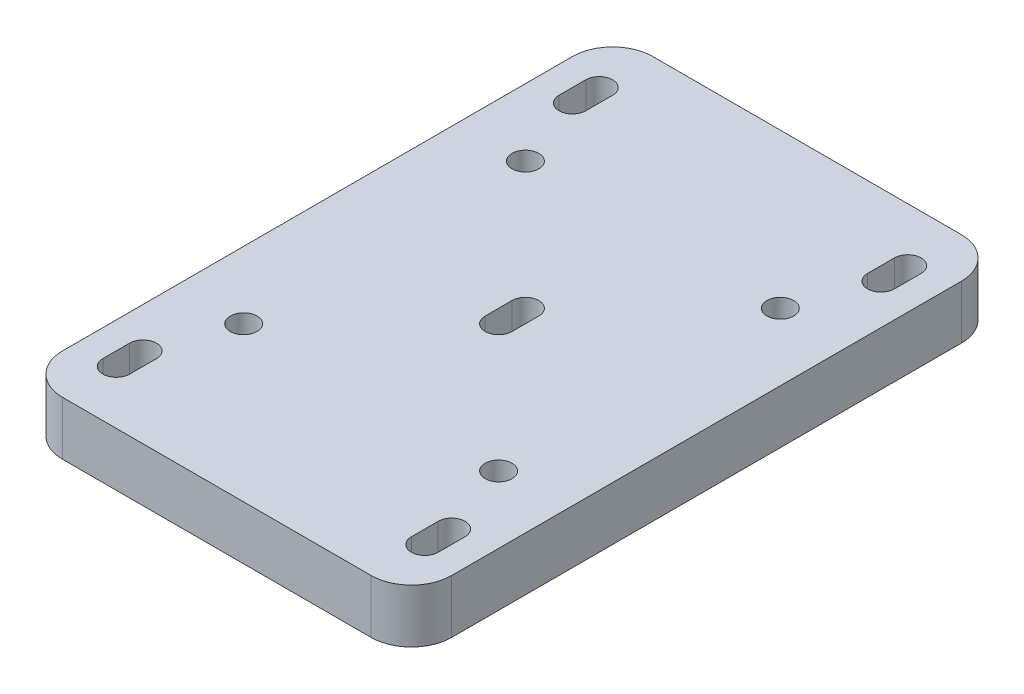
SolidWorks part; units mm, degrees
ref_plane "Front Plane" through (0, 0, 0) normal (0, 0, 1) x (1, 0, 0)
ref_plane "Top Plane" through (0, 0, 0) normal (0, 1, 0) x (1, 0, 0)
ref_plane "Right Plane" through (0, 0, 0) normal (1, 0, 0) x (0, 0, -1)
sketch "Sketch1" plane through (0, 0, 0) normal (0, 1, 0) x (1, 0, 0)
  line L1 (0, 0) -> (92.075, 0)
  line L2 (0, 0) -> (0, 139.7)
  line L3 (0, 139.7) -> (92.075, 139.7)
  line L4 (92.075, 0) -> (92.075, 139.7)
  dimension "D1" = 139.7
  dimension "D2" = 92.075
extrude "Boss-Extrude1" add sketch "Sketch1" along normal blind 12.7
hole_wizard "1/4 (0.25) Diameter Hole1" positions "Sketch5" profile "Sketch6" hole size "1/4" standard "ANSI Inch" end condition through all
sketch "Sketch5" plane through (0, 12.7, 0) normal (0, 1, 0) x (1, 0, 0)
  line L10 (0, 139.7) -> (92.075, 0) construction
  line L13 (15.875, 36.5125) -> (76.2, 36.5125) construction
  line L14 (15.875, 36.5125) -> (15.875, 103.1875) construction
  line L15 (15.875, 103.1875) -> (76.2, 103.1875) construction
  line L16 (76.2, 36.5125) -> (76.2, 103.1875) construction
  line L17 (15.875, 36.5125) -> (76.2, 103.1875) construction
  line L18 (15.875, 103.1875) -> (76.2, 36.5125) construction
  point P53 (46.0375, 69.85)
  point P54 (76.2, 103.1875)
  point P57 (15.875, 36.5125)
  point P58 (15.875, 103.1875)
  point P59 (76.2, 36.5125)
  dimension "D1" = 66.675
  dimension "D2" = 60.325
sketch "Sketch6" plane through (76.2, 12.7, -36.5125) normal (1, 0, 0) x (0, 0, 1)
  line L0 (0, 0) -> (0, 12.7)
  line L1 (0, 12.7) -> (3.175, 12.7)
  line L2 (3.175, 12.7) -> (3.175, 0)
  line L5 (3.175, 0) -> (0, 0)
  line L11 (0, -6.35) -> (0, 107.95) construction
  dimension "Thru Hole Dia." = 6.35
  dimension "Thru Hole Depth" = 12.7
sketch "Sketch7" plane through (0, 12.7, 0) normal (0, 1, 0) x (1, 0, 0)
  line L0 (0, 139.7) -> (92.075, 0) construction
  line L1 (92.075, 139.7) -> (0, 139.7) construction
  line L2 (9.525, 15.875) -> (82.55, 15.875) construction
  line L3 (9.525, 15.875) -> (9.525, 123.825) construction
  line L4 (9.525, 123.825) -> (82.55, 123.825) construction
  line L5 (82.55, 15.875) -> (82.55, 123.825) construction
  line L6 (9.525, 15.875) -> (82.55, 123.825) construction
  line L7 (9.525, 123.825) -> (82.55, 15.875) construction
  line L8 (92.075, 0) -> (92.075, 139.7) construction
  line L9 (9.525, 127) -> (9.525, 120.65) construction
  line L10 (12.7, 127) -> (12.7, 120.65)
  line L11 (6.35, 127) -> (6.35, 120.65)
  arc A0 (12.7, 127) -> (6.35, 127) centre (9.525, 127) ccw
  arc A1 (6.35, 120.65) -> (12.7, 120.65) centre (9.525, 120.65) ccw
  point P4 (46.0375, 69.85)
  point P15 (9.525, 123.825)
  point P21 (9.525, 123.825)
  dimension "D1" = 15.875
  dimension "D2" = 9.525
  dimension "D3" = 6.35
  dimension "D4" = 6.35
extrude "Cut-Extrude1" cut sketch "Sketch7" against normal blind 12.7
sketch "Sketch10" plane through (0, 12.7, 0) normal (0, 1, 0) x (1, 0, 0)
  line L0 (0, 139.7) -> (92.075, 0) construction
  line L2 (82.55, 15.875) -> (9.525, 15.875) construction
  line L3 (82.55, 15.875) -> (82.55, 123.825) construction
  line L4 (82.55, 123.825) -> (9.525, 123.825) construction
  line L5 (9.525, 15.875) -> (9.525, 123.825) construction
  line L6 (82.55, 15.875) -> (9.525, 123.825) construction
  line L7 (82.55, 123.825) -> (9.525, 15.875) construction
  point P4 (46.0375, 69.85)
  point P10 (82.55, 123.825)
  point P11 (82.55, 15.875)
  point P12 (9.525, 15.875)
pattern_sketch "Sketch-Pattern1" of "Cut-Extrude1" driven by "Sketch10"
fillet "Fillet1" radius 9.525 4 edges at (92.075, 6.35, 0) (0, 6.35, 0) (0, 6.35, -139.7) (92.075, 6.35, -139.7)
